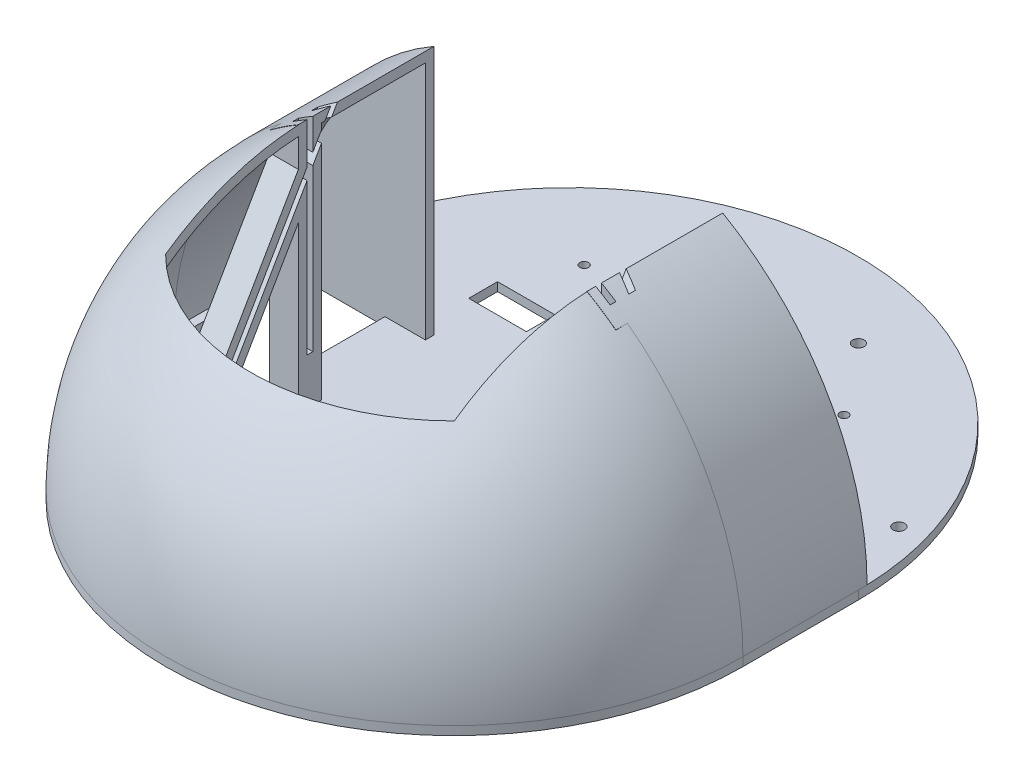
SolidWorks part; units mm, degrees
ref_plane "前视基准面" through (0, 0, 0) normal (0, 0, 1) x (1, 0, 0)
ref_plane "上视基准面" through (0, 0, 0) normal (0, 1, 0) x (1, 0, 0)
ref_plane "右视基准面" through (0, 0, 0) normal (1, 0, 0) x (0, 0, -1)
sketch "草图1" plane through (0, 0, 0) normal (0, 1, 0) x (1, 0, 0)
  line L1 (100, 0) -> (-100, 0)
  line L2 (100, 0) -> (100, 40)
  line L3 (100, 40) -> (-100, 40)
  line L4 (-100, 0) -> (-100, 40)
  circle A0 centre (0, 0) radius 100
  circle A1 centre (0, 40) radius 100
  dimension "D1" = 200
  dimension "D2" = 40
extrude "基础板" add sketch "草图1" along normal blind 3 contours L4 L3 L2 L1 | A0 | A1
sketch "草图3" plane through (0, 3, 0) normal (0, 1, 0) x (1, 0, 0)
  line L0 (0, 13.3527) -> (0, 34.0531)
  line L1 (-94, 40) -> (-64, 40)
  line L2 (-94, 40) -> (-94, 0)
  line L3 (-94, 0) -> (-64, 0)
  line L4 (-64, 40) -> (-64, 0)
  line L5 (64, 40) -> (64, 0)
  line L6 (94, 0) -> (64, 0)
  line L7 (94, 40) -> (94, 0)
  line L8 (94, 40) -> (64, 40)
  line L9 (-100, 0) -> (-100, 40) construction
  line L10 (35, 70) -> (35, 60)
  line L11 (-10, -67) -> (10, -67)
  line L12 (-10, -67) -> (-10, -37)
  line L13 (-10, -37) -> (10, -37)
  line L14 (10, -67) -> (10, -37)
  line L15 (-10, -67) -> (10, -37) construction
  line L16 (-10, -37) -> (10, -67) construction
  line L17 (-55, 70) -> (-35, 70)
  line L18 (-55, 70) -> (-55, 60)
  line L19 (-55, 60) -> (-35, 60)
  line L20 (-35, 70) -> (-35, 60)
  line L21 (55, 60) -> (35, 60)
  line L22 (55, 70) -> (55, 60)
  line L23 (55, 70) -> (35, 70)
  point P13 (0, -52)
  dimension "D1" = 6
  dimension "D2" = 30
  dimension "D3" = 52
  dimension "D4" = 30
  dimension "D5" = 20
  dimension "D6" = 60
  dimension "D7" = 35
  dimension "D8" = 20
  dimension "D9" = 10
extrude "过孔" cut sketch "草图3" against normal blind 3 contours L4 L1 L2 L3 | L7 L8 L5 L6 | L11 L14 L13 L12 | L20 L17 L18 L19 | L22 L23 L10 L21 region at (-79, 3, -20) region at (79, 3, -20) region at (45, 3, -65) region at (0, 3, 52) region at (-45, 3, -65)
sketch "草图2" plane through (0, 3, 0) normal (0, 1, 0) x (1, 0, 0)
  line L0 (0, -7.8134) -> (0, -32.4764)
  circle A0 centre (-45, -22) radius 2
  circle A1 centre (-40, -82) radius 2
  circle A2 centre (-88, 66) radius 2
  circle A3 centre (-26, 66) radius 2
  circle A4 centre (-26, 114) radius 2
  circle A5 centre (40, -82) radius 2
  circle A6 centre (45, -22) radius 2
  circle A7 centre (26, 114) radius 2
  circle A8 centre (26, 66) radius 2
  circle A9 centre (88, 66) radius 2
  circle A10 centre (-45, 90) radius 1.5
  circle A11 centre (45, 90) radius 1.5
  dimension "D1" = 4
  dimension "D2" = 4
  dimension "D3" = 4
  dimension "D4" = 4
  dimension "D5" = 4
  dimension "D6" = 45
  dimension "D7" = 22
  dimension "D8" = 40
  dimension "D9" = 82
  dimension "D10" = 26
  dimension "D11" = 88
  dimension "D12" = 26
  dimension "D13" = 66
  dimension "D14" = 66
  dimension "D15" = 114
  dimension "D16" = 3
  dimension "D17" = 90
  dimension "D18" = 45
extrude "螺丝孔" cut sketch "草图2" against normal through all contours A2 | A3 | A4 | A7 | A8 | A9 | A0 | A6 | A1 | A5 | A10 | A11 region at (-45, 3, 22) region at (-40, 3, 82) region at (-88, 3, -66) region at (-26, 3, -66) region at (-26, 3, -114) region at (40, 3, 82) region at (45, 3, 22) region at (26, 3, -114) region at (26, 3, -66) region at (88, 3, -66) region at (-45, 3, -90) region at (45, 3, -90)
sketch "草图18" plane through (0, 3, 0) normal (0, 1, 0) x (1, 0, 0)
  line L0 (-100, 0) -> (100, 0)
  arc A0 (-100, 0) -> (100, 0) centre (0, 0) ccw construction
  arc A1 (-100, 0) -> (100, 0) centre (0, 0) ccw
  arc A2 (-97, 0) -> (97, 0) centre (0, 0) ccw
  dimension "D1" = 3
revolve "弧形罩（后）" add sketch "草图18" angle 90 about L0 region at (-98.5, 3, 2.2361) reverse direction yes
sketch "草图19" plane through (0, 0, 0) normal (0, 0, -1) x (-1, 0, 0)
  line L2 (97, 3) -> (100, 3)
  line L3 (-100, 3) -> (-97, 3)
  line L4 (97, 3) -> (100, 3)
  line L5 (-100, 3) -> (-97, 3)
  arc A2 (97, 3) -> (-97, 3) centre (0, 3) ccw
  arc A3 (100, 3) -> (-100, 3) centre (0, 3) ccw
  arc A4 (97, 3) -> (-97, 3) centre (0, 3) ccw
  arc A5 (100, 3) -> (-100, 3) centre (0, 3) ccw
  dimension "D1" = 0
extrude "弧形罩（中）" add sketch "草图19" along normal blind 40
sketch "草图8" plane through (0, 3, 0) normal (0, 1, 0) x (1, 0, 0)
  line L2 (-60, 4) -> (-50, 4)
  line L3 (-60, 4) -> (-60, -4)
  line L4 (-60, -4) -> (-50, -4)
  line L5 (-50, 4) -> (-50, -4)
  line L6 (-60, 4) -> (-50, -4) construction
  line L7 (-60, -4) -> (-50, 4) construction
  point P1 (-55, 0)
  point P4 (0, 0)
  dimension "D1" = 55
  dimension "D2" = 8
  dimension "D5" = 10
extrude "安装架-L-树莓派" add sketch "草图8" along normal blind 100 contours L5 L2 L3 L4 region at (-55, 3, 0)
sketch "草图11" plane through (-60, 0, 0) normal (-1, 0, 0) x (0, 0, 1)
  line L0 (37, 3) -> (4, 60.1577)
  line L1 (100, 3) -> (0, 3) construction
  line L2 (4, 103) -> (4, 82.8999) construction
  line L3 (46.2376, 3) -> (3.7581, 76.5767)
  line L4 (67, 3) -> (37, 3) construction
  line L6 (3.7581, 76.5767) -> (4, 60.1577)
  line L7 (37, 3) -> (46.2376, 3)
  dimension "D1" = 37
  dimension "D2" = 60
  dimension "D3" = 60
  dimension "D4" = 8
extrude "安装架-L-32" add sketch "草图11" against normal blind 10
sketch "草图16" plane through (-50, 0, 0) normal (1, 0, 0) x (0, 0, -1)
  line L0 (-40.4641, 3) -> (-32.4641, 16.8564)
  line L1 (-37, 3) -> (-46.2376, 3) construction
  line L2 (0, 3) -> (-100, 3) construction
  line L3 (-4, 60.1577) -> (-37, 3) construction
  line L4 (-32.4641, 16.8564) -> (-34.1962, 17.8564)
  line L5 (-32.4641, 16.8564) -> (17.5359, 103.4589)
  line L6 (-34.1962, 17.8564) -> (15.8038, 104.4589)
  line L7 (17.5359, 103.4589) -> (15.8038, 104.4589)
  line L8 (4, 3) -> (-4, 3) construction
  line L10 (4, 103) -> (-4, 103) construction
  line L11 (-1, 19) -> (1, 19)
  line L12 (-1, 19) -> (-1, 103)
  line L13 (-1, 103) -> (1, 103)
  line L14 (1, 19) -> (1, 103)
  line L15 (4, 103) -> (4, 89.6025) construction
  line L16 (-4, 60.1577) -> (-4, 3) construction
  dimension "D1" = 60
  dimension "D2" = 3
  dimension "D3" = 16
  dimension "D4" = 2
  dimension "D5" = 16
  dimension "D6" = 3
  dimension "D7" = 3
  dimension "D8" = 100
extrude "安装架-L-凹槽" cut sketch "草图16" against normal blind 5 contours L4 L6 L7 L5 | L14 L13 L12 L11
mirror "安装架-R" about plane through (0, 0, 0) normal (1, 0, 0) of "安装架-L-凹槽", "安装架-L-32", "安装架-L-树莓派"
sketch "草图23" plane through (0, 3, 0) normal (0, 1, 0) x (1, 0, 0)
  line L1 (-100, 40) -> (100, 40)
  line L2 (-100, 40) -> (-100, 43)
  line L3 (-100, 43) -> (100, 43)
  line L4 (100, 40) -> (100, 43)
  dimension "D1" = 3
extrude "封闭墙" add sketch "草图23" along normal blind 100
sketch "草图24" plane through (0, 0, -40) normal (0, 0, 1) x (1, 0, 0)
  line L0 (-150, 3) -> (150, 3)
  arc A0 (100, 3) -> (0, 103) centre (0, 3) ccw construction
  arc A1 (100, 3) -> (0, 103) centre (0, 3) ccw
  arc A2 (0, 103) -> (-100, 3) centre (0, 3) ccw construction
  arc A3 (0, 103) -> (-100, 3) centre (0, 3) ccw
  arc A4 (150, 3) -> (0, 153) centre (0, 3) ccw
  arc A5 (0, 153) -> (-150, 3) centre (0, 3) ccw
  line M1 (100, 103) -> (0, 103)
  arc M2 (0, 103) -> (100, 3) centre (0, 3) cw
  line M3 (100, 3) -> (100, 103)
  dimension "D1" = 50
extrude "消除凸出" cut sketch "草图24" against normal blind 100 and the other way blind 100 contours A4 A5 L0 A3 M1 M3 | M3 M1 M2 region at (-103.6943, 106.6943, -40) region at (77.6632, 80.6632, -40)
sketch "草图21" plane through (0, 3, 0) normal (0, 1, 0) x (1, 0, 0)
  line L1 (50, 50) -> (-50, 50)
  line L2 (50, 50) -> (50, -50)
  line L3 (50, -50) -> (-50, -50)
  line L4 (-50, 50) -> (-50, -50)
  line L5 (50, 50) -> (-50, -50) construction
  line L6 (50, -50) -> (-50, 50) construction
  circle A0 centre (0, 0) radius 70.7107
  point P0 (0, 0)
  line M23 (10, -37) -> (10, -67)
  line M24 (10, -67) -> (-10, -67)
  line M25 (-10, -67) -> (-10, -37)
  dimension "D1" = 100
  dimension "D2" = 100
extrude "天窗开口" cut sketch "草图21" along normal blind 100 contours L3 A0 | L3 M23 M25 M24 | L4 L3 L2 L1 region at (0, 3, 69.6895) region at (0, 3, 58.5)
